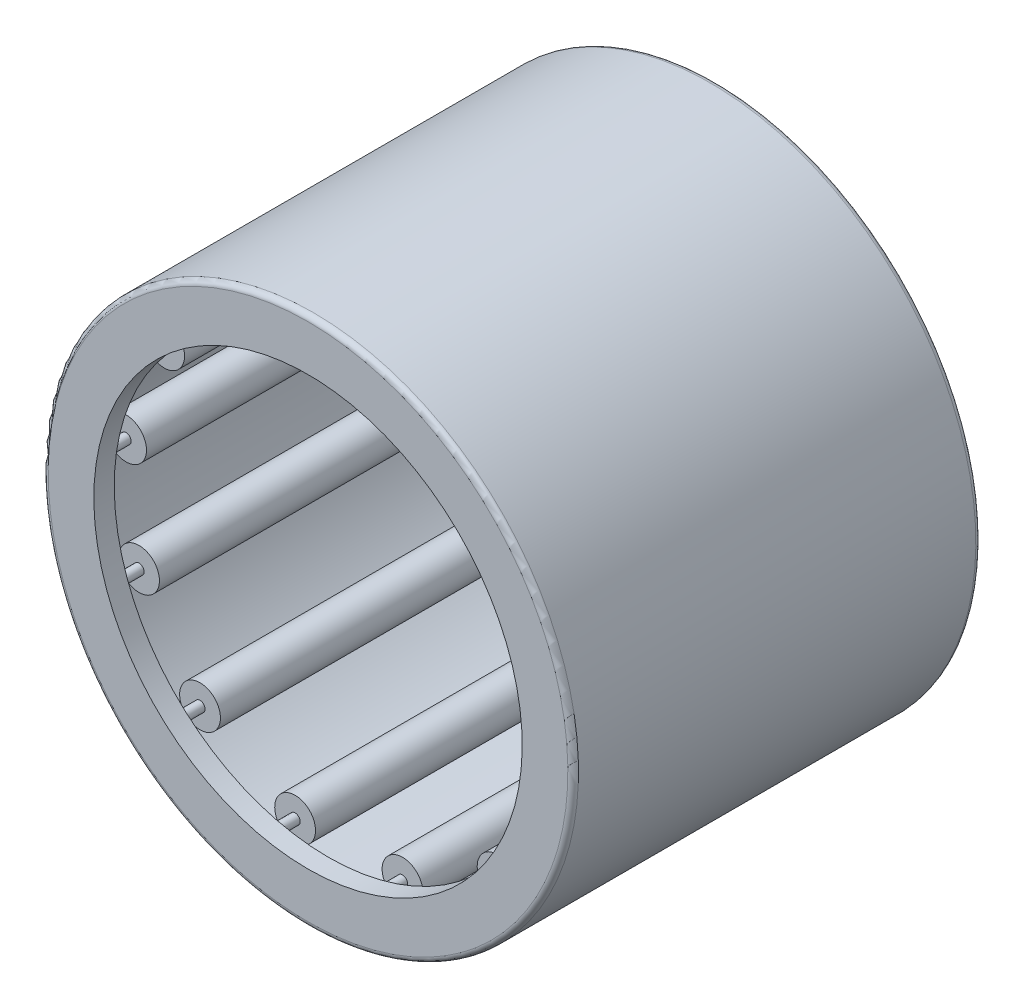
SolidWorks part; units mm, degrees
ref_plane "Front Plane" through (0, 0, 0) normal (0, 0, 1) x (1, 0, 0)
ref_plane "Top Plane" through (0, 0, 0) normal (0, 1, 0) x (1, 0, 0)
ref_plane "Right Plane" through (0, 0, 0) normal (1, 0, 0) x (0, 0, -1)
sketch "Sketch1" plane through (0, 0, 0) normal (1, 0, 0) x (0, 0, -1)
  line L0 (-7.9375, 0) -> (7.9375, 0) construction
  line L1 (0, 0) -> (0, 10.3187) construction
  line L2 (-7.9375, 0) -> (-7.9375, 10.3188) construction
  line L3 (-7.9375, 10.3188) -> (7.9375, 10.3188)
  line L4 (7.9375, 10.3188) -> (7.9375, 0) construction
  line L5 (7.9375, 0) -> (7.1438, 0) construction
  line L6 (7.1438, 0) -> (7.1438, 9.525) construction
  line L7 (7.1438, 9.525) -> (-7.1438, 9.525)
  line L8 (-7.1438, 9.525) -> (-7.1438, 0) construction
  line L9 (-7.1438, 0) -> (-7.9375, 0) construction
  line L10 (-7.9375, 10.3188) -> (-7.9375, 8.3344)
  line L11 (-7.9375, 8.3344) -> (-7.1438, 8.3344)
  line L12 (-7.1438, 8.3344) -> (-7.1438, 9.525)
  line L13 (7.1438, 10.3188) -> (7.1438, 9.525) construction
  line L14 (7.1438, 9.525) -> (7.1438, 8.3344)
  line L15 (7.1438, 8.3344) -> (7.9375, 8.3344)
  line L16 (7.9375, 8.3344) -> (7.9375, 10.3188)
  line L17 (7.1438, 9.525) -> (7.1438, 8.7312) construction
  line L18 (7.1438, 8.7312) -> (7.1438, 7.9375) construction
  point P5 (0, 7.9375)
  dimension "Width" = 15.875
  dimension "OD" = 20.6375
  dimension "Shaft Dia" = 15.875
revolve "Revolve1" add sketch "Sketch1" angle 360 about L0
sketch "Sketch2" plane through (0, 0, 0) normal (1, 0, 0) x (0, 0, -1)
  line L0 (7.1438, 9.525) -> (-7.1438, 9.525) construction
  line L1 (-6.35, 8.7312) -> (6.35, 8.7313) construction
  line L2 (-6.35, 8.7312) -> (-6.35, 9.525) construction
  line L3 (-6.35, 9.525) -> (6.35, 9.525)
  line L4 (6.35, 8.7313) -> (6.35, 9.525) construction
  line L5 (7.1438, 8.3344) -> (7.9375, 8.3344) construction
  line L6 (-7.1438, 8.7312) -> (-6.35, 8.7312) construction
  line L7 (6.35, 8.7313) -> (7.1438, 8.7312) construction
  line L8 (-7.9375, 8.3344) -> (-7.1438, 8.3344) construction
  line L9 (-6.35, 8.9297) -> (-6.35, 8.5328) construction
  line L10 (-7.1438, 8.7312) -> (-7.1438, 8.3344) construction
  line L11 (-6.35, 9.525) -> (-6.35, 8.9297)
  line L12 (6.35, 9.525) -> (6.35, 8.9297)
  line L13 (6.35, 8.9297) -> (-6.35, 8.9297)
  line L14 (0, 9.525) -> (0, 7.9375) construction
  line L15 (-7.1438, 8.3344) -> (-7.1438, 9.525) construction
  line L16 (-6.35, 8.5328) -> (-7.1438, 8.5328) construction
  line L17 (0, 0) -> (7.9375, 0) construction
  line L31 (7.9375, -10.3188) -> (7.9375, 10.3188) construction
  point P16 (0, 8.7312)
revolve "Revolve2" add sketch "Sketch2" angle 360 about L1
sketch "Sketch3" plane through (0, 0, 0) normal (1, 0, 0) x (0, 0, -1)
  line L0 (7.1438, 9.525) -> (7.1438, 8.3344) construction
  line L1 (-7.1438, 8.7312) -> (7.1438, 8.7312)
  line L2 (-7.1438, 8.7312) -> (-7.1438, 8.9297)
  line L3 (-7.1438, 8.9297) -> (7.1438, 8.9297)
  line L4 (7.1438, 8.7312) -> (7.1438, 8.9297)
  line L5 (0, 0) -> (7.9375, 0) construction
  line L6 (7.9375, -10.3188) -> (7.9375, 10.3188) construction
revolve "Revolve3" add sketch "Sketch3" angle 360 about L1
ref_axis "Axis1" through (0, 0, -7.9375) along (0, 0, 1)
pattern_circular "CirPattern1" count 13 every 27.692 about axis through (0, 0, -7.9375) along (0, 0, 1) of bodies 166 167
fillet "Fillet1" radius 0.2064 2 edges at (0, -10.3188, -7.9375) (0, -10.3188, 7.9375)
sketch "Sketch4" plane through (0, 0, 0) normal (1, 0, 0) x (0, 0, -1)
  line L1 (7.7311, 7.9375) -> (6.35, 7.9375)
  line L2 (7.7311, 7.9375) -> (7.7311, 8.3344)
  line L3 (7.7311, 8.3344) -> (6.35, 8.3344)
  line L4 (6.35, 7.9375) -> (6.35, 8.3344)
  line L5 (-7.9375, 8.3344) -> (-7.1438, 8.3344) construction
  line L6 (7.7311, -10.3188) -> (7.7311, 10.3188) construction
  line L7 (6.35, 9.525) -> (6.35, 8.9297) construction
revolve "Revolve4" [suppressed] add sketch "Sketch4" angle 360 about L0
sketch "Sketch5" plane through (0, 0, 0) normal (1, 0, 0) x (0, 0, -1)
  line L0 (-7.7311, 10.3188) -> (-7.7311, -10.3188) construction
  line L1 (-6.35, 7.9375) -> (-7.7311, 7.9375)
  line L2 (-6.35, 7.9375) -> (-6.35, 8.3344)
  line L3 (-6.35, 8.3344) -> (-7.7311, 8.3344)
  line L4 (-7.7311, 7.9375) -> (-7.7311, 8.3344)
  line L6 (-6.35, 9.525) -> (-6.35, 8.9297) construction
  line L7 (-7.9375, 8.3344) -> (-7.1438, 8.3344) construction
revolve "Revolve5" [suppressed] add sketch "Sketch5" angle 360 about L0
sketch "Front View" plane through (0, 0, 0) normal (0, 0, 1) x (1, 0, 0)
  circle A0 centre (0, 0) radius 7.9375 construction
  circle A1 centre (0, 0) radius 10.3187 construction
  dimension "OD" = 20.6375
  dimension "ID" = 15.875
sketch "Right View" plane through (0, 0, 0) normal (1, 0, 0) x (0, 0, -1)
  line L0 (-7.9375, 10.3187) -> (7.9375, 10.3187) construction
  dimension "Width" = 15.875
ref_axis "Center Axis 1" through (0, 0, -7.7311) along (0, 0, 1)
ref_plane "Contact Plane 1" through (0, 0, 7.9375) normal (0, 0, 1) x (1, 0, 0)
ref_plane "Contact Plane 2" through (0, 0, -7.9375) normal (0, 0, -1) x (-1, 0, 0)
equation "\"Rollers@CirPattern1\" = \"OD@Sketch1\"*16"
equation "\"D1@Fillet1\" = \"OD@Sketch1\"*.01"
equation "\"Angle@CirPattern1\"= 360 / \"Rollers@CirPattern1\""
equation "\"OD@Front View\"=\"OD@Sketch1\""
equation "\"ID@Front View\"=\"Shaft Dia@Sketch1\""
equation "\"Width@Right View\"=\"Width@Sketch1\""
